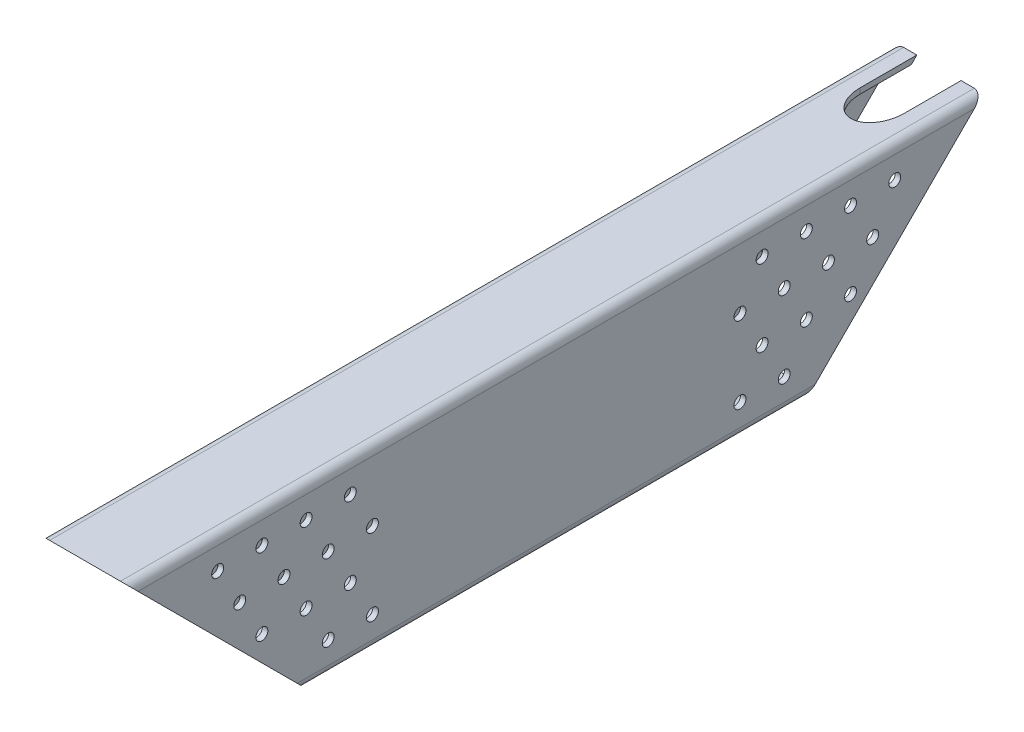
SolidWorks part; units mm, degrees
material "6061-T6 (SS)"
ref_plane "Front" through (0, 0, 0) normal (0, 0, 1) x (1, 0, 0)
ref_plane "Top" through (0, 0, 0) normal (0, 1, 0) x (1, 0, 0)
ref_plane "Right" through (0, 0, 0) normal (1, 0, 0) x (0, 0, -1)
sketch "Sketch3" plane through (0, 0, 0) normal (1, 0, 0) x (0, 0, -1)
  line L0 (-50.8, -25.4) -> (-194.4841, -25.4)
  line L1 (-194.4841, -25.4) -> (-245.2841, 25.4)
  line L2 (-245.2841, 25.4) -> (0, 25.4)
  line L3 (0, 25.4) -> (-50.8, -25.4)
  point P8 (-25.4, 0)
  dimension "D1" = 50.8
  dimension "D2" = 101.6
  dimension "D3" = 45
sketch "Sketch1" plane through (0, 0, 0) normal (0, 0, 1) x (1, 0, 0)
  line L1 (-10.16, -25.4) -> (10.16, -25.4)
  line L2 (-12.7, -22.86) -> (-12.7, 22.86)
  line L3 (-10.16, 25.4) -> (10.16, 25.4)
  line L4 (12.7, -22.86) -> (12.7, 22.86)
  line L5 (-12.7, -25.4) -> (12.7, 25.4) construction
  line L6 (-12.7, 25.4) -> (12.7, -25.4) construction
  arc A0 (-10.16, -25.4) -> (-12.7, -22.86) centre (-10.16, -22.86) cw
  arc A1 (10.16, -25.4) -> (12.7, -22.86) centre (10.16, -22.86) ccw
  arc A2 (10.16, 25.4) -> (12.7, 22.86) centre (10.16, 22.86) cw
  arc A3 (-12.7, 22.86) -> (-10.16, 25.4) centre (-10.16, 22.86) cw
  point P0 (0, 0)
  dimension "D3" = 2.54
  dimension "D1" = 25.4
  dimension "D2" = 50.8
extrude "Extrude-Thin1" add sketch "Sketch1" along normal up to vertex (245.2841 mm away) thin up to point (0, 25.4, 245.2841) thin type one direction reverse wall 1.5875
sketch "Sketch2" plane through (12.7, 0, 0) normal (1, 0, 0) x (0, 0, -1)
  line L0 (-245.2841, 25.4) -> (-194.4841, -25.4)
  line L1 (-245.2841, -25.4) -> (0, -25.4) construction
  line L2 (-194.4841, -25.4) -> (-245.2841, -25.4)
  line L3 (-245.2841, -25.4) -> (-245.2841, 25.4)
  line L4 (0, 25.4) -> (-50.8, -25.4)
  line L5 (-50.8, -25.4) -> (0, -25.4)
  line L6 (0, -25.4) -> (0, 25.4)
  line L7 (0, 25.4) -> (-50.8, -25.4) construction
  line L8 (-194.4841, -25.4) -> (-245.2841, 25.4) construction
extrude "Cut-Extrude1" cut sketch "Sketch2" against normal through all
sketch "Sketch4" plane through (0, 12.7, 12.7) normal (0, -0.7071, -0.7071) x (1, 0, 0)
  circle A0 centre (0, -22.3185) radius 6.35
  circle A1 centre (0, -6.4435) radius 6.35
  circle A2 centre (0, -38.1935) radius 6.35
  dimension "D1" = 12.7
extrude "Cut-Extrude2" cut sketch "Sketch4" against normal through all
sketch "Sketch5" plane through (0, 25.4, 0) normal (0, 1, 0) x (1, 0, 0)
  line L0 (-6.35, -16.2876) -> (-6.35, 0)
  line L1 (-6.35, 0) -> (6.35, 0)
  line L2 (6.35, 0) -> (6.35, -16.2876)
  line L3 (-4.6185, 0) -> (-10.16, 0) construction
  ellipse E1 centre (0, -16.2876) end of major axis (0, -7.3073) minor radius 6.35 construction
  ellipse E3 centre (0, -16.2876) end of major axis (0, -7.3073) minor radius 6.35 (-6.35, -16.2876) -> (6.35, -16.2876) ccw
extrude "Cut-Extrude3" cut sketch "Sketch5" against normal through all
hole_wizard "1/8 (0.135) Diameter Hole1" positions "Sketch6" profile "Sketch7" hole size "1/8" standard "ANSI Inch" end condition through all
sketch "Sketch6" plane through (-12.7, 0, 0) normal (-1, 0, 0) x (0, 0, 1)
  point P78 (63.5, 16.4978)
  point P81 (57.15, 5.4993)
  point P84 (50.8, 16.4978)
  point P87 (38.1, 16.4978)
  point P90 (25.4, 16.4978)
  point P93 (31.75, 5.4993)
  point P96 (44.45, 5.4993)
  point P99 (38.1, -5.4993)
  point P102 (50.8, -5.4993)
  point P105 (63.5, -5.4993)
  point P108 (57.15, -16.4978)
  point P111 (69.85, -16.4978)
  point P116 (181.7841, 16.4978)
  point P119 (194.4841, 16.4978)
  point P122 (207.1841, 16.4978)
  point P125 (219.8841, 16.4978)
  point P128 (213.5341, 5.4993)
  point P131 (200.8341, 5.4993)
  point P134 (188.1341, 5.4993)
  point P137 (175.4341, 5.4993)
  point P140 (181.7841, -5.4993)
  point P143 (194.4841, -5.4993)
  point P146 (207.1841, -5.4993)
  point P149 (188.1341, -16.4978)
  point P152 (175.4341, -16.4978)
  point P155 (69.85, 5.4993)
sketch "Sketch7" plane through (-12.7, 16.4978, 63.5) normal (0, 1, 0) x (0, 0, 1)
  line L0 (0, 0) -> (0, 25.4)
  line L1 (0, 25.4) -> (1.7145, 25.4)
  line L2 (1.7145, 25.4) -> (1.7145, 0)
  line L5 (1.7145, 0) -> (0, 0)
  line L11 (0, -6.35) -> (0, 107.95) construction
  dimension "Thru Hole Dia." = 3.429
  dimension "Thru Hole Depth" = 25.4
